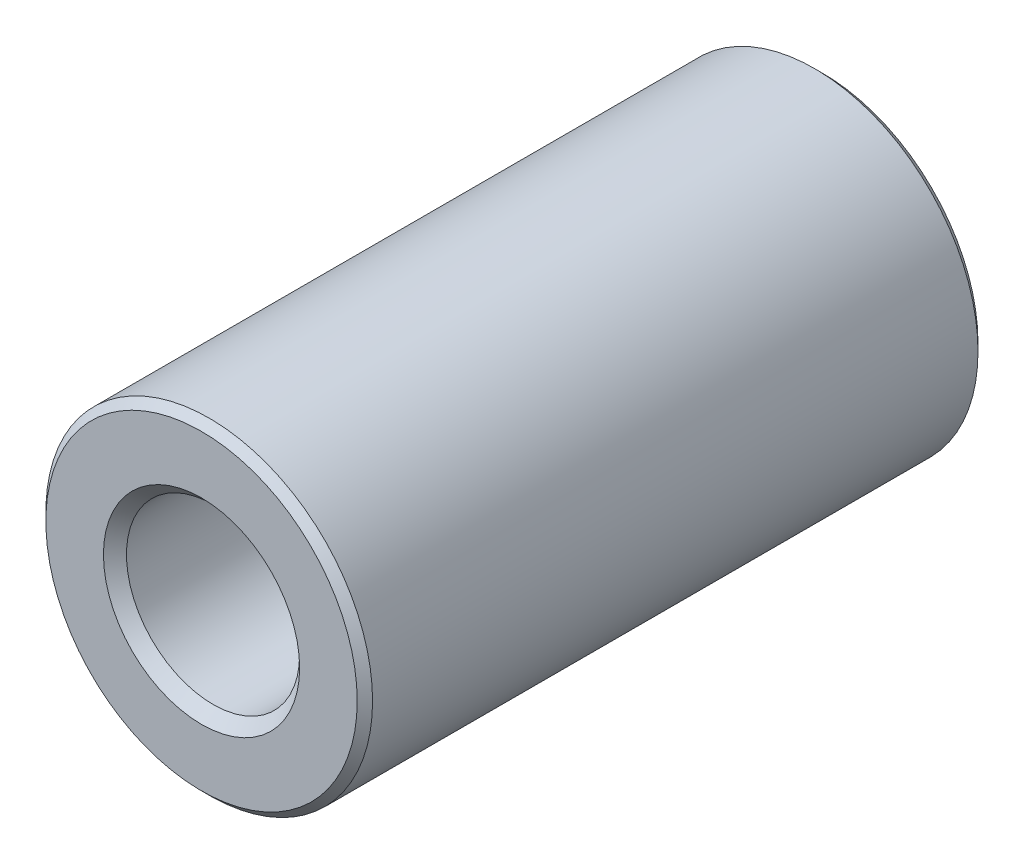
SolidWorks part; units mm, degrees
ref_plane "Front Plane" through (0, 0, 0) normal (0, 0, 1) x (1, 0, 0)
ref_plane "Top Plane" through (0, 0, 0) normal (0, 1, 0) x (1, 0, 0)
ref_plane "Right Plane" through (0, 0, 0) normal (1, 0, 0) x (0, 0, -1)
sketch "Sketch1" plane through (0, 0, 0) normal (0, 0, 1) x (1, 0, 0)
  circle A0 centre (0, 0) radius 5 construction
  circle A1 centre (0, 0) radius 2.65 construction
  point P4 (0, 5)
  dimension "ID" = 5.3
  dimension "OD" = 10
sketch "Sketch2" plane through (0, 0, 0) normal (1, 0, 0) x (0, 0, -1)
  line L0 (-9.5, 5) -> (9.5, 5) construction
  dimension "Length" = 19
sketch "Sketch3" plane through (0, 0, 0) normal (0, 0, 1) x (1, 0, 0)
  circle A0 centre (0, 0) radius 2.65 construction
  circle A1 centre (0, 0) radius 5 construction
  circle A2 centre (0, 0) radius 2.65
  circle A3 centre (0, 0) radius 5
extrude "Boss-Extrude1" add sketch "Sketch3" against normal up to vertex (9.5 mm away) and the other way up to vertex (9.5 mm away) up to point (0, 5, -9.5) other way up to point (0, 5, 9.5)
chamfer "Chamfer1" distance 0.235 angle 45 2 edges at (5, 0, 9.5) (5, 0, -9.5)
chamfer "Chamfer2" distance 0.3525 angle 45 2 edges at (2.65, 0, 9.5) (2.65, 0, -9.5)
equation "\"D1@Chamfer1\"=(\"OD@Sketch1\"-\"ID@Sketch1\")*0.05"
equation "\"D1@Chamfer2\"=(\"OD@Sketch1\"-\"ID@Sketch1\")*0.075"
